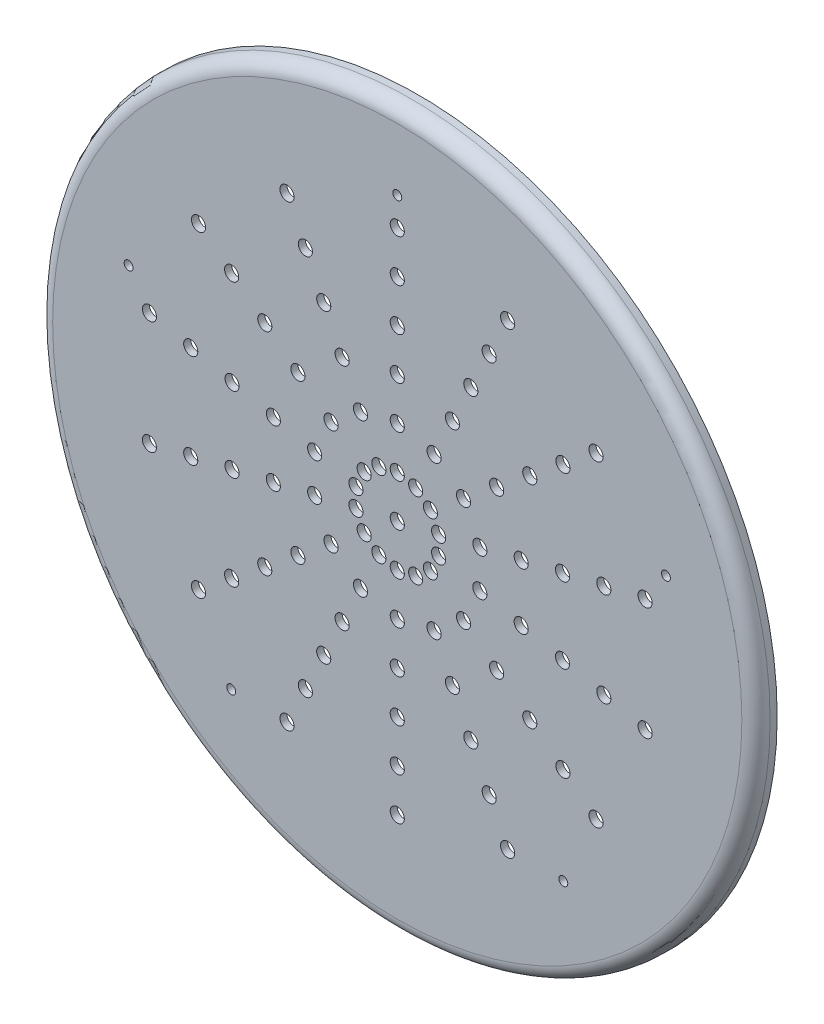
SolidWorks part; units mm, degrees
material "1060 Alloy"
ref_plane "Front Plane" through (0, 0, 0) normal (0, 0, 1) x (1, 0, 0)
ref_plane "Top Plane" through (0, 0, 0) normal (0, 1, 0) x (1, 0, 0)
ref_plane "Right Plane" through (0, 0, 0) normal (1, 0, 0) x (0, 0, -1)
sketch "Sketch2" plane through (0, 0, 0) normal (0, 0, 1) x (1, 0, 0)
  circle A0 centre (0, 0) radius 254
extrude "Boss-Extrude1" add sketch "Sketch2" along normal blind 15
fillet "Fillet1" radius 10 1 edges at (254, 0, 15)
shell "Shell1" thickness 5 removed face at (254, 0, 0)
sketch "Sketch3" plane through (0, 0, 15) normal (0, 0, 1) x (1, 0, 0)
  circle A0 centre (0, 200) radius 3.175
  circle A1 centre (0, 0) radius 244 construction
  circle A2 centre (190.2113, 61.8034) radius 3.175
  circle A3 centre (117.5571, -161.8034) radius 3.175
  circle A4 centre (-117.5571, -161.8034) radius 3.175
  circle A5 centre (-190.2113, 61.8034) radius 3.175
  point P17 (0, 0)
  dimension "D1" = 6.35
  dimension "D2" = 200
  dimension "D4" = 117.5571
  dimension "D5" = 190.2113
  dimension "D3" = 5
extrude "Cut-Extrude1" cut sketch "Sketch3<7>" against normal blind 10
sketch "Sketch3<7>" plane through (0, 0, 15) normal (0, 0, 1) x (1, 0, 0) same geometry as "Sketch3"
extrude "Extrude-Thin1" add sketch "Sketch3" against normal blind 10 thin contours A2 | A0 | A5 | A4 | A3 thin type one direction wall 1
sketch "Sketch5" plane through (0, 0, 10) normal (0, 0, -1) x (-1, 0, 0)
  circle A0 centre (0, 180) radius 5
  circle A1 centre (0, 150) radius 5
  circle A2 centre (0, 120) radius 5
  circle A3 centre (0, 90) radius 5
  circle A4 centre (0, 60) radius 5
  circle A5 centre (0, 30) radius 5
  circle A6 centre (0, 0) radius 5
  circle A7 centre (0, 0) radius 5
  circle A8 centre (13.0165, 27.0291) radius 5
  circle A9 centre (26.033, 54.0581) radius 5
  circle A10 centre (39.0495, 81.0872) radius 5
  circle A11 centre (52.066, 108.1163) radius 5
  circle A12 centre (65.0826, 135.1453) radius 5
  circle A13 centre (78.0991, 162.1744) radius 5
  circle A14 centre (0, 0) radius 5
  circle A15 centre (23.4549, 18.7047) radius 5
  circle A16 centre (46.9099, 37.4094) radius 5
  circle A17 centre (70.3648, 56.1141) radius 5
  circle A18 centre (93.8198, 74.8188) radius 5
  circle A19 centre (117.2747, 93.5235) radius 5
  circle A20 centre (140.7297, 112.2282) radius 5
  circle A21 centre (0, 0) radius 5
  circle A22 centre (29.2478, 6.6756) radius 5
  circle A23 centre (58.4957, 13.3513) radius 5
  circle A24 centre (87.7435, 20.0269) radius 5
  circle A25 centre (116.9913, 26.7025) radius 5
  circle A26 centre (146.2392, 33.3781) radius 5
  circle A27 centre (175.487, 40.0538) radius 5
  circle A28 centre (0, 0) radius 5
  circle A29 centre (29.2478, -6.6756) radius 5
  circle A30 centre (58.4957, -13.3513) radius 5
  circle A31 centre (87.7435, -20.0269) radius 5
  circle A32 centre (116.9913, -26.7025) radius 5
  circle A33 centre (146.2392, -33.3781) radius 5
  circle A34 centre (175.487, -40.0538) radius 5
  circle A35 centre (0, 0) radius 5
  circle A36 centre (23.4549, -18.7047) radius 5
  circle A37 centre (46.9099, -37.4094) radius 5
  circle A38 centre (70.3648, -56.1141) radius 5
  circle A39 centre (93.8198, -74.8188) radius 5
  circle A40 centre (117.2747, -93.5235) radius 5
  circle A41 centre (140.7297, -112.2282) radius 5
  circle A42 centre (0, 0) radius 5
  circle A43 centre (13.0165, -27.0291) radius 5
  circle A44 centre (26.033, -54.0581) radius 5
  circle A45 centre (39.0495, -81.0872) radius 5
  circle A46 centre (52.066, -108.1163) radius 5
  circle A47 centre (65.0826, -135.1453) radius 5
  circle A48 centre (78.0991, -162.1744) radius 5
  circle A49 centre (0, 0) radius 5
  circle A50 centre (0, -30) radius 5
  circle A51 centre (0, -60) radius 5
  circle A52 centre (0, -90) radius 5
  circle A53 centre (0, -120) radius 5
  circle A54 centre (0, -150) radius 5
  circle A55 centre (0, -180) radius 5
  circle A56 centre (0, 0) radius 5
  circle A57 centre (-13.0165, -27.0291) radius 5
  circle A58 centre (-26.033, -54.0581) radius 5
  circle A59 centre (-39.0495, -81.0872) radius 5
  circle A60 centre (-52.066, -108.1163) radius 5
  circle A61 centre (-65.0826, -135.1453) radius 5
  circle A62 centre (-78.0991, -162.1744) radius 5
  circle A63 centre (0, 0) radius 5
  circle A64 centre (-23.4549, -18.7047) radius 5
  circle A65 centre (-46.9099, -37.4094) radius 5
  circle A66 centre (-70.3648, -56.1141) radius 5
  circle A67 centre (-93.8198, -74.8188) radius 5
  circle A68 centre (-117.2747, -93.5235) radius 5
  circle A69 centre (-140.7297, -112.2282) radius 5
  circle A70 centre (0, 0) radius 5
  circle A71 centre (-29.2478, -6.6756) radius 5
  circle A72 centre (-58.4957, -13.3513) radius 5
  circle A73 centre (-87.7435, -20.0269) radius 5
  circle A74 centre (-116.9913, -26.7025) radius 5
  circle A75 centre (-146.2392, -33.3781) radius 5
  circle A76 centre (-175.487, -40.0538) radius 5
  circle A77 centre (0, 0) radius 5
  circle A78 centre (-29.2478, 6.6756) radius 5
  circle A79 centre (-58.4957, 13.3513) radius 5
  circle A80 centre (-87.7435, 20.0269) radius 5
  circle A81 centre (-116.9913, 26.7025) radius 5
  circle A82 centre (-146.2392, 33.3781) radius 5
  circle A83 centre (-175.487, 40.0538) radius 5
  circle A84 centre (0, 0) radius 5
  circle A85 centre (-23.4549, 18.7047) radius 5
  circle A86 centre (-46.9099, 37.4094) radius 5
  circle A87 centre (-70.3648, 56.1141) radius 5
  circle A88 centre (-93.8198, 74.8188) radius 5
  circle A89 centre (-117.2747, 93.5235) radius 5
  circle A90 centre (-140.7297, 112.2282) radius 5
  circle A91 centre (0, 0) radius 5
  circle A92 centre (-13.0165, 27.0291) radius 5
  circle A93 centre (-26.033, 54.0581) radius 5
  circle A94 centre (-39.0495, 81.0872) radius 5
  circle A95 centre (-52.066, 108.1163) radius 5
  circle A96 centre (-65.0826, 135.1453) radius 5
  circle A97 centre (-78.0991, 162.1744) radius 5
  point P187 (0, 0)
  dimension "D1" = 7
  dimension "D3" = 10
  dimension "D2" = 30
  dimension "D4" = 14
extrude "Cut-Extrude3" cut sketch "Sketch5" against normal blind 10 contours A27 | A5 | A92 | A78 | A29 | A82 | A73 | A65 | A67 | A0 | A1 | A2 | A97 | A13 | A12 | A20 | A19 | A10 | A11 | A3 | A94 | A95 | A96 | A88 | A89 | A90 | A87 | A86 | A93 | A4 | A9 | A16 | A17 | A18 | A24 | A25 | A26 | A23 | A15 | A22 | A8 | A85 | A6 | A71 | A64 | A57 | A50 | A43 | A36 | A79 | A80 | A81 | A83 | A76 | A75 | A74 | A72 | A66 | A68 | A69 | A59 | A58 | A60 | A61 | A62 | A51 | A52 | A53 | A54 | A55 | A48 | A46 | A47 | A45 | A44 | A37 | A30 | A31 | A32 | A33 | A34 | A41 | A40 | A39 | A38 region at (0, 30, 10) region at (-175.487, 40.0538, 10) region at (-29.2478, -6.6756, 10) region at (46.9099, -37.4094, 10) region at (93.8198, -74.8188, 10) region at (87.7435, -20.0269, 10) region at (29.2478, 6.6756, 10) region at (146.2392, 33.3781, 10) region at (13.0165, 27.0291, 10)
